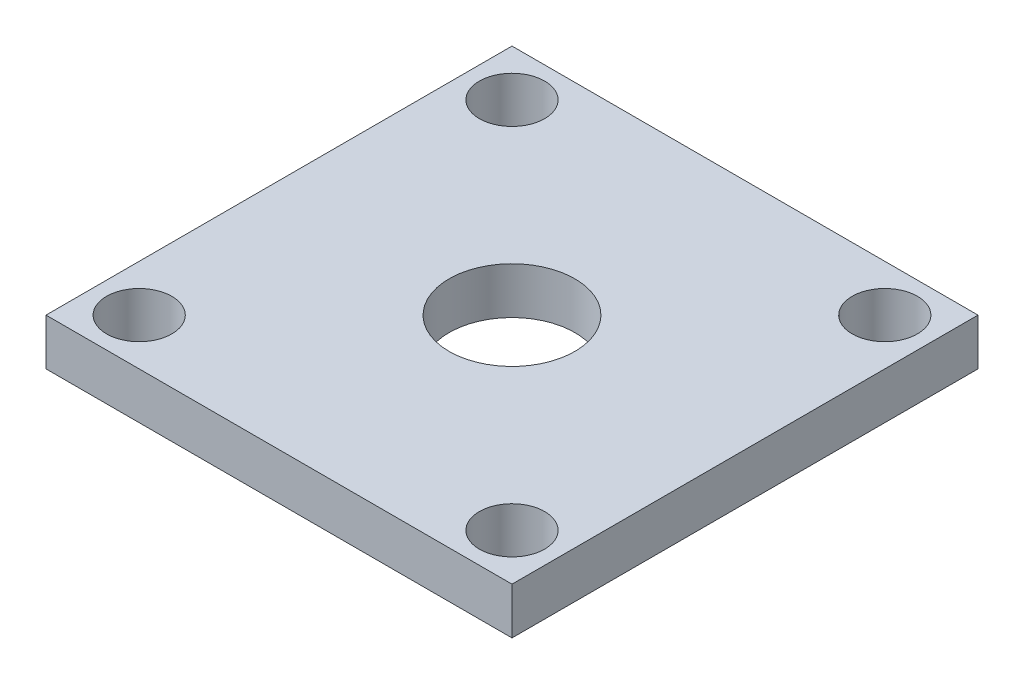
SolidWorks part; units mm, degrees
ref_plane "前视基准面" through (0, 0, 0) normal (0, 0, 1) x (1, 0, 0)
ref_plane "上视基准面" through (0, 0, 0) normal (0, 1, 0) x (1, 0, 0)
ref_plane "右视基准面" through (0, 0, 0) normal (1, 0, 0) x (0, 0, -1)
other "Configuration Table"
sketch "草图1" plane through (0, 0, 0) normal (0, 1, 0) x (1, 0, 0)
  line L0 (-5, 5) -> (-3, 3)
  line L1 (-5, 5) -> (5, 5)
  line L2 (-5, 5) -> (-5, -5)
  line L3 (-5, -5) -> (5, -5)
  line L4 (5, 5) -> (5, -5)
  line L5 (-5, 5) -> (5, -5) construction
  line L6 (-5, -5) -> (5, 5) construction
  line L7 (-3, 3) -> (3, 3)
  line L8 (-3, 3) -> (-3, -3)
  line L9 (-3, -3) -> (3, -3)
  line L10 (3, 3) -> (3, -3)
  line L11 (-3, 3) -> (3, -3) construction
  line L12 (-3, -3) -> (3, 3) construction
  line L13 (3, -3) -> (5, -5)
  circle A0 centre (0, 0) radius 1.35
  circle A1 centre (-4, 4) radius 0.7
  circle A2 centre (4, -4) radius 0.7
  circle A3 centre (4, 4) radius 0.7
  circle A4 centre (-4, -4) radius 0.7
  point P0 (0, 0)
  point P5 (0, 0)
  dimension "D1" = 2.7
  dimension "D4" = 1.4
  dimension "D2" = 6
  dimension "D3" = 10
extrude "凸台-拉伸1" add sketch "草图1" along normal blind 1 contours A2 L13 L4 L1 L0 A1 L7 L10 A3 | A2 L13 L9 L8 L0 A1 L2 L3 A4 | L10 L7 L8 L9 A0 region at (0, 0, -4.8586) region at (-4.8475, 0, -4.6475) region at (0, 0, -2.9151)
